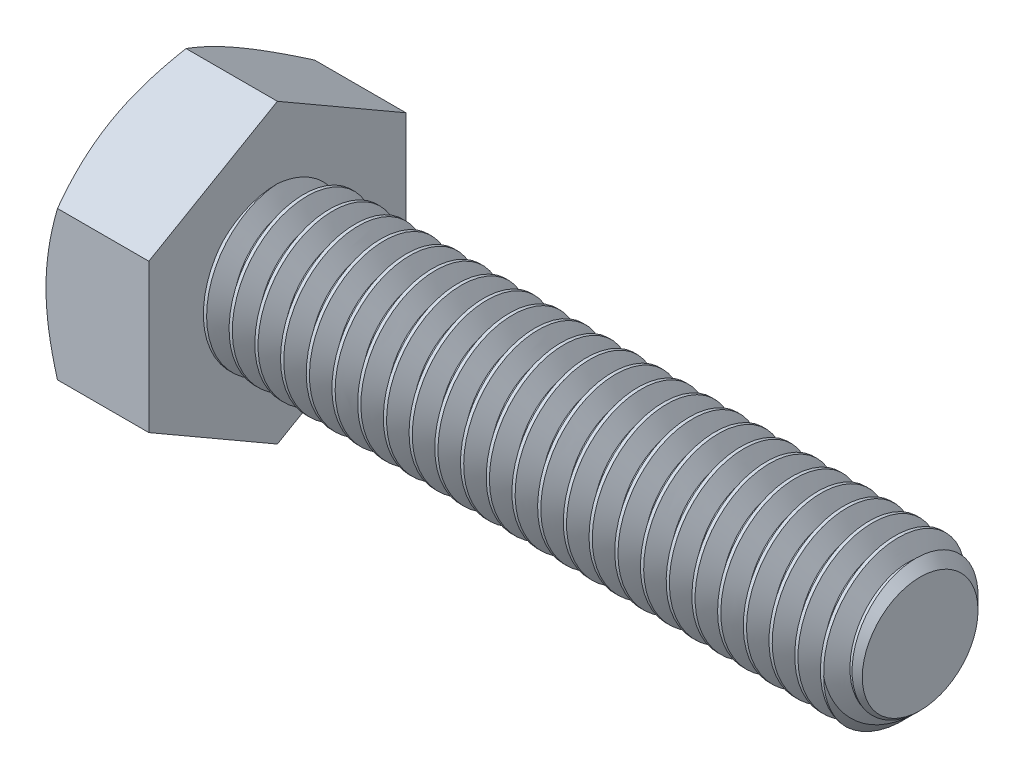
SolidWorks part; units mm, degrees
ref_plane "Front Plane" through (0, 0, 0) normal (0, 0, 1) x (1, 0, 0)
ref_plane "Top Plane" through (0, 0, 0) normal (0, 1, 0) x (1, 0, 0)
ref_plane "Right Plane" through (0, 0, 0) normal (1, 0, 0) x (0, 0, -1)
sketch "Sketch1" plane through (0, 0, 0) normal (0, 0, 1) x (1, 0, 0)
  line L0 (-14.5, 0) -> (14.5, 0) construction
  line L1 (-10.5, 5) -> (-10.5, -5) construction
  line L2 (-14.5, 5) -> (-14.5, -5) construction
  line L3 (14.5, 3) -> (14.5, -3) construction
  point P8 (11, -3)
  dimension "Thread Dia" = 6
  dimension "Hex" = 10
  dimension "Head Ht" = 4
  dimension "Length" = 25
  dimension "D1" = 3.5
ref_plane "Plane2" through (14.5, 0, 0) normal (1, 0, 0) x (0, 0, -1)
sketch "Sketch2" plane through (14.5, 0, 0) normal (1, 0, 0) x (0, 0, -1)
  circle A0 centre (0, 0) radius 3
extrude "Boss-Extrude1" add sketch "Sketch2" against normal up to vertex (25 mm away) up to point (-10.5, -5, 0)
sketch "Sketch4" plane through (14.5, 0, 0) normal (1, 0, 0) x (0, 0, -1)
  circle A1 centre (0, 0) radius 3
  circle A2 centre (0, 0) radius 3
  dimension "D1" = 0
curve "Helix/Spiral1" pitch 1 height 26 turns 26 parameters "Pitch"=1
chamfer "Chamfer1" distance 0.75 angle 45 1 edges at (14.5, 0, -3)
sketch "Sketch5" plane through (0, 0, 0) normal (0, 0, 1) x (1, 0, 0)
  line L0 (14.5, 3) -> (14.875, 2.3505)
  line L1 (14.875, 2.3505) -> (15, 2.3505)
  line L2 (15, 2.3505) -> (15.375, 3)
  line L3 (14.5, 3) -> (15.375, 3)
  line L4 (14.9375, 2.3505) -> (14.9375, 3) construction
  line L5 (14.6875, 2.6752) -> (15.1875, 2.6752) construction
  line L6 (14.5, -3) -> (14.5, 3) construction
  dimension "D1" = 60
  dimension "D2" = 0.125
  dimension "D3" = 0.5
sweep "Cut-Sweep1" cut profiles "Sketch5" path "Helix/Spiral1"
sketch "Sketch3" plane through (-10.5, 0, 0) normal (-1, 0, 0) x (0, 0, 1)
  line L0 (0, 5) -> (0, -5) construction
  line L1 (-5, -2.8868) -> (0, -5.7735)
  line L2 (0, -5.7735) -> (5, -2.8868)
  line L3 (5, -2.8868) -> (5, 2.8868)
  line L4 (5, 2.8868) -> (0, 5.7735)
  line L5 (0, 5.7735) -> (-5, 2.8868)
  line L6 (-5, 2.8868) -> (-5, -2.8868)
  circle A0 centre (0, 0) radius 5 construction
extrude "Boss-Extrude2" add sketch "Sketch3" along normal up to vertex (4 mm away) up to point (-14.5, -5, 0)
sketch "Sketch6" plane through (-14.5, 0, 0) normal (-1, 0, 0) x (0, 0, 1)
  circle A0 centre (0, 0) radius 5 construction
  circle A1 centre (0, 0) radius 5
extrude "Cut-Extrude1" cut sketch "Sketch6" against normal through all draft 60 flip side to cut
sketch "Sketch9" plane through (0, 0, 0) normal (0, 0, 1) x (1, 0, 0)
  line L0 (-10.5, 3) -> (-10.5, 0)
  line L1 (-10.5, 0) -> (-36.5, 0)
  line L2 (-36.5, 0) -> (-39.5, 3)
  line L3 (-39.5, 3) -> (-10.5, 3)
  line L4 (-14.5, 0) -> (14.5, 0) construction
  line L5 (-10.5, 5) -> (-10.5, -5) construction
  line L6 (14.5, 3) -> (14.5, -3) construction
  dimension "D1" = 45
  dimension "MinThreadLg" = 54
revolve "Revolve1" [suppressed] add sketch "Sketch9" angle 360 about L1
equation "\"D2@Sketch5\" = \"Pitch@Helix/Spiral1\"*.125"
equation "\"D3@Sketch5\" = \"Pitch@Helix/Spiral1\"*.50"
equation "\"D3@Helix/Spiral1\" = \"Length@Sketch1\"+\"Pitch@Helix/Spiral1\""
equation "\"D1@Chamfer1\" = \"Pitch@Helix/Spiral1\"*.750"
equation "\"D1@Sketch1\" = \"Pitch@Helix/Spiral1\"*3.50"
